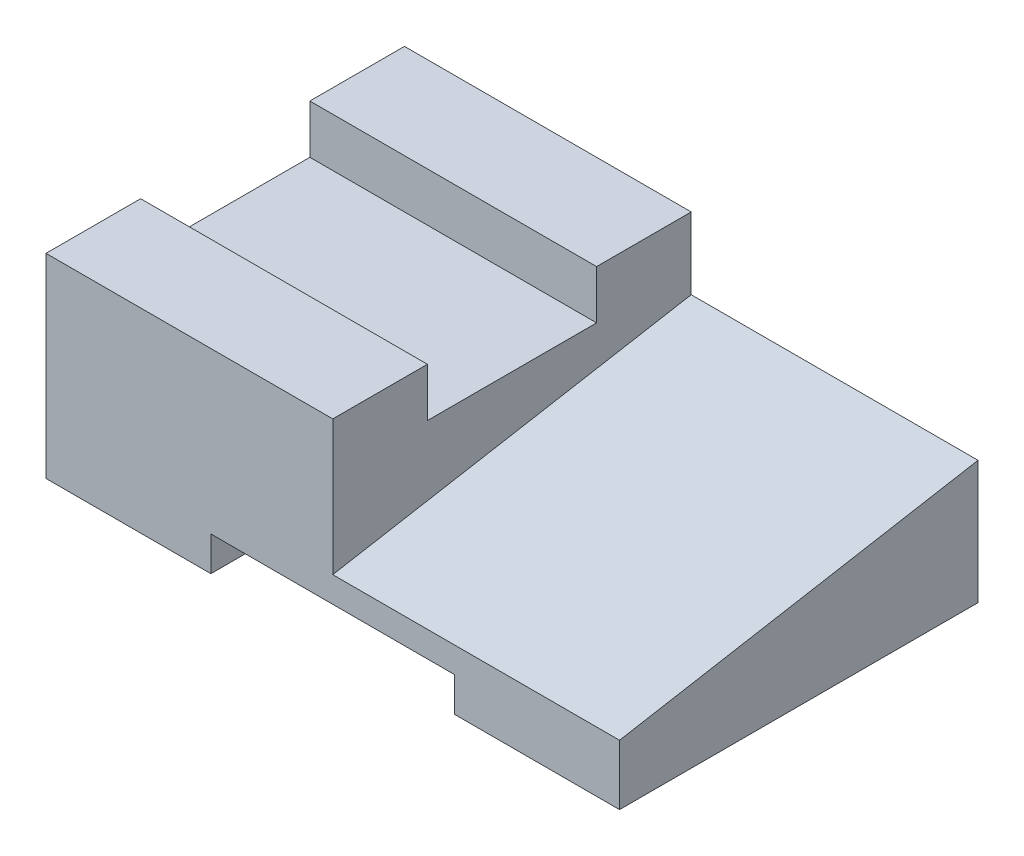
SolidWorks part; units mm, degrees
ref_plane "Front Plane" through (0, 0, 0) normal (0, 0, 1) x (1, 0, 0)
ref_plane "Top Plane" through (0, 0, 0) normal (0, 1, 0) x (1, 0, 0)
ref_plane "Right Plane" through (0, 0, 0) normal (1, 0, 0) x (0, 0, -1)
sketch "Sketch3" plane through (0, 0, 0) normal (1, 0, 0) x (0, 0, -1)
  line L0 (0, 68) -> (0, 0)
  line L1 (0, 0) -> (125, 0)
  line L2 (125, 0) -> (125, 68)
  line L3 (125, 68) -> (92, 68)
  line L4 (92, 68) -> (92, 51)
  line L5 (92, 51) -> (33, 51)
  line L6 (33, 51) -> (33, 68)
  line L7 (33, 68) -> (0, 68)
  line L8 (125, 43) -> (0, 20.9591)
  dimension "D1" = 10
  dimension "D2" = 68
  dimension "D3" = 17
  dimension "D4" = 33
  dimension "D5" = 125
  dimension "D6" = 33
  dimension "D7" = 25
extrude "Boss-Extrude3" add sketch "Sketch3" against normal blind 100 contours L8 L2 L3 L4 L5 L6 L7 L0 | L7 L0 L1 L2 L3 L4 L5 L6 region at (0, 46.5411, -54.2992)
extrude "Boss-Extrude4" add sketch "Sketch3<3>" along normal blind 100 contours L2 L8 L0 L1 region at (0, 16.6227, -69.6793)
sketch "Sketch3<3>" plane through (0, 0, 0) normal (1, 0, 0) x (0, 0, -1) same geometry as "Sketch3"
sketch "Sketch4" plane through (0, 0, 0) normal (0, 0, 1) x (1, 0, 0)
  line L0 (-42.5, 0) -> (-42.5, 12)
  line L1 (-100, 0) -> (100, 0) construction
  line L2 (-42.5, 12) -> (42.5, 12)
  line L3 (42.5, 12) -> (42.5, 0)
  point P4 (0, 12)
  dimension "D1" = 12
  dimension "D2" = 85
extrude "Cut-Extrude1" cut sketch "Sketch4" against normal blind 125 and the other way through all flip side to cut
